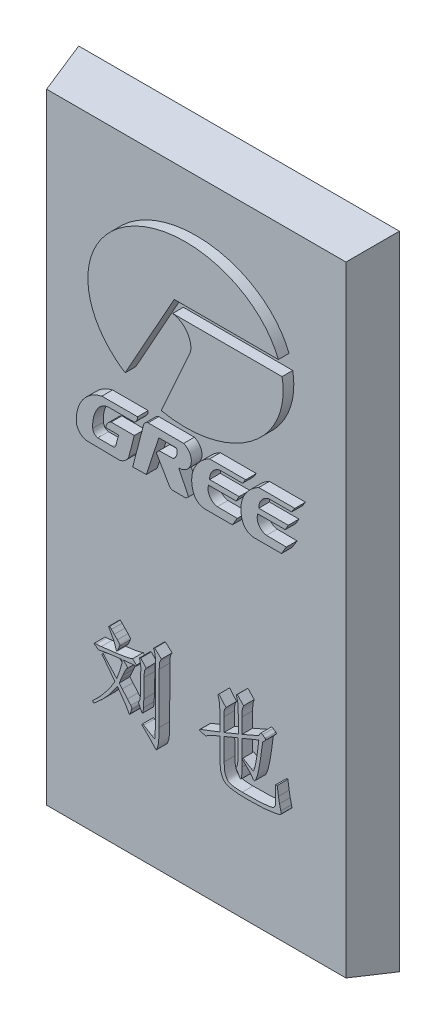
SolidWorks part; units mm, degrees
ref_plane "前视基准面" through (0, 0, 0) normal (0, 0, 1) x (1, 0, 0)
ref_plane "上视基准面" through (0, 0, 0) normal (0, 1, 0) x (1, 0, 0)
ref_plane "右视基准面" through (0, 0, 0) normal (1, 0, 0) x (0, 0, -1)
other "Configuration Table"
sketch "草图1" plane through (0, 0, 0) normal (0, 0, 1) x (1, 0, 0)
  line L18 (-15, -30) -> (15, -30)
  line L19 (-15, -30) -> (-15, 30)
  line L20 (-15, 30) -> (15, 30)
  line L21 (15, -30) -> (15, 30)
  line L22 (-15, -30) -> (15, 30) construction
  line L23 (-15, 30) -> (15, -30) construction
  point P0 (0, 0)
  dimension "D2" = 60
  dimension "D1" = 30
ref_plane "基准面1" through (0, 0, 4) normal (0, 0, 1) x (1, 0, 0)
sketch "草图2" plane through (0, 0, 4) normal (0, 0, 1) x (1, 0, 0)
  line L0 (-15, 30) -> (15, 30) construction
  line L1 (-14, -29) -> (14, -29)
  line L2 (-14, -29) -> (-14, 29)
  line L3 (-14, 29) -> (14, 29)
  line L4 (14, -29) -> (14, 29)
  line L5 (-14, -29) -> (14, 29) construction
  line L6 (-14, 29) -> (14, -29) construction
  line L7 (15, -30) -> (15, 30) construction
  point P0 (0, 0)
  dimension "D1" = 1
  dimension "D2" = 1
loft "放样1" add profiles "草图1", "草图2"
sketch "草图4" plane through (0, 0, 4) normal (0, 0, 1) x (1, 0, 0)
  line L6 (-14, -17) -> (14, -17) construction
  line L7 (-14, -29) -> (-14, 29) construction
  line L8 (14, -29) -> (14, 29) construction
  text T0 "刘也" font "汉仪长仿宋体" height 6
  dimension "D1" = 17
extrude "凸台-拉伸3" add sketch "草图4" along normal blind 1
sketch "草图5" plane through (0, 0, 0) normal (0, 0, -1) x (-1, 0, 0)
  line L4 (0, 18) -> (0, 0) construction
  line L5 (0, 0) -> (0, -18) construction
  line L6 (15, -30) -> (-15, -30) construction
  circle A7 centre (0, 0) radius 5.5
  circle A8 centre (0, 18) radius 5.5
  circle A9 centre (0, -18) radius 5.5
  dimension "D1" = 11
  dimension "D2" = 12
extrude "切除-拉伸1" cut sketch "草图5" against normal blind 2
sketch "草图7" plane through (0, 0, 4) normal (0, 0, 1) x (1, 0, 0)
  line L0 (3.2108, -13.9623) -> (1.3838, -14.6693) construction
  line L1 (1.3838, -14.8163) -> (1.8889, -14.9544) construction
  line L2 (3.2223, -14.2896) -> (3.2338, -16.284) construction
  line L3 (8.9065, -17.5088) -> (8.7864, -16.9911) construction
  line L4 (8.7864, -16.9911) -> (8.6892, -16.4387) construction
  line L5 (8.6892, -16.4387) -> (8.569, -15.6192) construction
  line L6 (8.569, -15.6192) -> (8.4258, -15.6358) construction
  line L7 (8.4258, -15.6358) -> (8.413, -17.2071) construction
  line L8 (3.6072, -16.1882) -> (3.5944, -14.1349) construction
  line L9 (3.5944, -14.1349) -> (4.9163, -13.5826) construction
  line L10 (4.9163, -13.5826) -> (4.9163, -14.7997) construction
  line L11 (4.832, -16.3186) -> (4.9892, -16.6024) construction
  line L12 (5.2654, -15.7918) -> (5.2654, -13.4445) construction
  line L13 (5.2654, -13.4445) -> (6.8507, -12.7976) construction
  line L14 (6.1782, -15.4901) -> (5.3728, -14.9979) construction
  line L15 (5.3728, -14.9979) -> (5.3012, -15.127) construction
  line L16 (5.3012, -15.127) -> (5.6131, -15.4211) construction
  line L17 (5.6131, -15.4211) -> (5.9737, -15.7918) construction
  line L18 (5.9737, -15.7918) -> (6.2984, -16.1971) construction
  line L19 (7.4401, -12.3744) -> (7.1882, -12.1839) construction
  line L20 (7.0195, -12.1583) -> (6.8277, -12.4524) construction
  line L21 (6.8277, -12.4524) -> (5.2769, -13.1249) construction
  line L22 (5.2769, -13.1249) -> (5.2769, -11.7185) construction
  line L23 (5.4214, -10.7341) -> (4.832, -10.1127) construction
  line L24 (4.832, -10.1127) -> (4.7361, -10.1997) construction
  line L25 (4.9291, -11.753) -> (4.9291, -13.2629) construction
  line L26 (4.9291, -13.2629) -> (3.5829, -13.8242) construction
  line L27 (3.5829, -13.8242) -> (3.5829, -12.547) construction
  line L28 (3.7746, -11.7006) -> (3.1149, -10.9412) construction
  line L29 (3.1149, -10.9412) -> (3.0178, -11.0447) construction
  line L30 (3.2108, -12.3744) -> (3.2108, -13.9623) construction
  line L31 (-2.8861, -10.2163) -> (-2.9948, -10.2853) construction
  line L32 (-2.8017, -11.5459) -> (-2.826, -16.4822) construction
  line L33 (-3.138, -17.4488) -> (-3.9076, -16.9744) construction
  line L34 (-3.9076, -16.9744) -> (-4.0035, -16.9054) construction
  line L35 (-4.0035, -16.9054) -> (-4.0994, -17.0089) construction
  line L36 (-4.0994, -17.0089) -> (-3.9677, -17.1547) construction
  line L37 (-3.9677, -17.1547) -> (-3.3553, -17.7505) construction
  line L38 (-3.3553, -17.7505) -> (-2.9219, -18.2248) construction
  line L39 (-2.4898, -16.4643) -> (-2.4655, -11.7185) construction
  line L40 (-2.2609, -10.7954) -> (-2.8861, -10.2163) construction
  line L41 (-4.1838, -12.4434) -> (-4.1953, -12.8142) construction
  line L42 (-4.1953, -12.8142) -> (-4.2323, -14.6437) construction
  line L43 (-4.3525, -15.5323) -> (-4.2554, -15.7138) construction
  line L44 (-4.2554, -15.7138) -> (-4.148, -15.9209) construction
  line L45 (-3.9434, -15.5847) -> (-3.9076, -14.8598) construction
  line L46 (-3.9076, -14.8598) -> (-3.8718, -13.0814) construction
  line L47 (-3.6915, -12.2453) -> (-4.1953, -11.675) construction
  line L48 (-4.1953, -11.675) -> (-4.3154, -11.7275) construction
  line L49 (-8.702, -17.3887) -> (-8.6061, -17.5344) construction
  line L50 (-8.6061, -17.5344) -> (-8.4731, -17.4309) construction
  line L51 (-5.5658, -16.215) -> (-5.4214, -16.4822) construction
  line L52 (-5.4214, -16.4822) -> (-5.3255, -16.6638) construction
  line L53 (-5.1695, -16.6638) -> (-5.0608, -16.2917) construction
  line L54 (-5.1209, -15.9734) -> (-5.4341, -15.6103) construction
  line L55 (-5.4341, -15.6103) -> (-5.9264, -15.049) construction
  line L56 (-5.9264, -15.049) -> (-6.214, -14.7128) construction
  line L57 (-6.214, -14.7128) -> (-6.0823, -14.411) construction
  line L58 (-6.0823, -14.411) -> (-5.8535, -13.8932) construction
  line L59 (-5.4098, -13.0993) -> (-5.7934, -12.6505) construction
  line L60 (-5.7934, -12.6505) -> (-5.1938, -12.5905) construction
  line L61 (-5.1938, -12.5905) -> (-4.6287, -12.547) construction
  line L62 (-4.5929, -12.4434) -> (-4.9649, -12.1238) construction
  line L63 (-7.885, -12.5905) -> (-8.3657, -12.625) construction
  line L64 (-8.4859, -12.7452) -> (-8.2328, -12.9356) construction
  line L65 (-8.2328, -12.9356) -> (-8.1612, -12.9957) construction
  line L66 (-8.1612, -12.9957) -> (-7.9566, -12.9523) construction
  line L67 (-7.9566, -12.9523) -> (-7.4516, -12.8577) construction
  line L68 (-7.4516, -12.8577) -> (-6.9722, -12.7886) construction
  line L69 (-6.9722, -12.7886) -> (-5.9506, -12.6672) construction
  line L70 (-5.9506, -12.6672) -> (-5.9506, -12.8577) construction
  line L71 (-7.6447, -13.1594) -> (-7.729, -13.0737) construction
  line L72 (-7.729, -13.0737) -> (-7.8249, -13.1773) construction
  line L73 (-7.8249, -13.1773) -> (-7.729, -13.3064) construction
  line L74 (-8.6176, -17.3017) -> (-8.702, -17.3887) construction
  line L75 (-7.2113, -10.6305) -> (-7.1154, -10.7775) construction
  line L76 (-6.9722, -11.0537) -> (-6.8034, -11.3554) construction
  line L77 (-6.5273, -12.0292) -> (-6.503, -12.1149) construction
  line L78 (-6.3112, -12.0292) -> (-6.191, -11.7185) construction
  line L79 (-6.3828, -11.2953) -> (-6.6717, -10.9936) construction
  line L80 (-6.6717, -10.9936) -> (-6.9351, -10.7264) construction
  line L81 (-6.9351, -10.7264) -> (-7.1039, -10.5538) construction
  line L82 (-7.1039, -10.5538) -> (-7.2113, -10.6305) construction
  line L83 (3.2108, -13.9623) -> (1.3838, -14.6693)
  line L84 (1.3838, -14.8163) -> (1.8889, -14.9544)
  line L85 (3.2223, -14.2896) -> (3.2338, -16.284)
  line L86 (8.9065, -17.5088) -> (8.7864, -16.9911)
  line L87 (8.7864, -16.9911) -> (8.6892, -16.4387)
  line L88 (8.6892, -16.4387) -> (8.569, -15.6192)
  line L89 (8.569, -15.6192) -> (8.4258, -15.6358)
  line L90 (8.4258, -15.6358) -> (8.413, -17.2071)
  line L91 (3.6072, -16.1882) -> (3.5944, -14.1349)
  line L92 (3.5944, -14.1349) -> (4.9163, -13.5826)
  line L93 (4.9163, -13.5826) -> (4.9163, -14.7997)
  line L94 (4.832, -16.3186) -> (4.9892, -16.6024)
  line L95 (5.2654, -15.7918) -> (5.2654, -13.4445)
  line L96 (5.2654, -13.4445) -> (6.8507, -12.7976)
  line L97 (6.1782, -15.4901) -> (5.3728, -14.9979)
  line L98 (5.3728, -14.9979) -> (5.3012, -15.127)
  line L99 (5.3012, -15.127) -> (5.6131, -15.4211)
  line L100 (5.6131, -15.4211) -> (5.9737, -15.7918)
  line L101 (5.9737, -15.7918) -> (6.2984, -16.1971)
  line L102 (7.4401, -12.3744) -> (7.1882, -12.1839)
  line L103 (7.0195, -12.1583) -> (6.8277, -12.4524)
  line L104 (6.8277, -12.4524) -> (5.2769, -13.1249)
  line L105 (5.2769, -13.1249) -> (5.2769, -11.7185)
  line L106 (5.4214, -10.7341) -> (4.832, -10.1127)
  line L107 (4.832, -10.1127) -> (4.7361, -10.1997)
  line L108 (4.9291, -11.753) -> (4.9291, -13.2629)
  line L109 (4.9291, -13.2629) -> (3.5829, -13.8242)
  line L110 (3.5829, -13.8242) -> (3.5829, -12.547)
  line L111 (3.7746, -11.7006) -> (3.1149, -10.9412)
  line L112 (3.1149, -10.9412) -> (3.0178, -11.0447)
  line L113 (3.2108, -12.3744) -> (3.2108, -13.9623)
  line L114 (-2.8861, -10.2163) -> (-2.9948, -10.2853)
  line L115 (-2.8017, -11.5459) -> (-2.826, -16.4822)
  line L116 (-3.138, -17.4488) -> (-3.9076, -16.9744)
  line L117 (-3.9076, -16.9744) -> (-4.0035, -16.9054)
  line L118 (-4.0035, -16.9054) -> (-4.0994, -17.0089)
  line L119 (-4.0994, -17.0089) -> (-3.9677, -17.1547)
  line L120 (-3.9677, -17.1547) -> (-3.3553, -17.7505)
  line L121 (-3.3553, -17.7505) -> (-2.9219, -18.2248)
  line L122 (-2.4898, -16.4643) -> (-2.4655, -11.7185)
  line L123 (-2.2609, -10.7954) -> (-2.8861, -10.2163)
  line L124 (-4.1838, -12.4434) -> (-4.1953, -12.8142)
  line L125 (-4.1953, -12.8142) -> (-4.2323, -14.6437)
  line L126 (-4.3525, -15.5323) -> (-4.2554, -15.7138)
  line L127 (-4.2554, -15.7138) -> (-4.148, -15.9209)
  line L128 (-3.9434, -15.5847) -> (-3.9076, -14.8598)
  line L129 (-3.9076, -14.8598) -> (-3.8718, -13.0814)
  line L130 (-3.6915, -12.2453) -> (-4.1953, -11.675)
  line L131 (-4.1953, -11.675) -> (-4.3154, -11.7275)
  line L132 (-8.702, -17.3887) -> (-8.6061, -17.5344)
  line L133 (-8.6061, -17.5344) -> (-8.4731, -17.4309)
  line L134 (-5.5658, -16.215) -> (-5.4214, -16.4822)
  line L135 (-5.4214, -16.4822) -> (-5.3255, -16.6638)
  line L136 (-5.1695, -16.6638) -> (-5.0608, -16.2917)
  line L137 (-5.1209, -15.9734) -> (-5.4341, -15.6103)
  line L138 (-5.4341, -15.6103) -> (-5.9264, -15.049)
  line L139 (-5.9264, -15.049) -> (-6.214, -14.7128)
  line L140 (-6.214, -14.7128) -> (-6.0823, -14.411)
  line L141 (-6.0823, -14.411) -> (-5.8535, -13.8932)
  line L142 (-5.4098, -13.0993) -> (-5.7934, -12.6505)
  line L143 (-5.7934, -12.6505) -> (-5.1938, -12.5905)
  line L144 (-5.1938, -12.5905) -> (-4.6287, -12.547)
  line L145 (-4.5929, -12.4434) -> (-4.9649, -12.1238)
  line L146 (-7.885, -12.5905) -> (-8.3657, -12.625)
  line L147 (-8.4859, -12.7452) -> (-8.2328, -12.9356)
  line L148 (-8.2328, -12.9356) -> (-8.1612, -12.9957)
  line L149 (-8.1612, -12.9957) -> (-7.9566, -12.9523)
  line L150 (-7.9566, -12.9523) -> (-7.4516, -12.8577)
  line L151 (-7.4516, -12.8577) -> (-6.9722, -12.7886)
  line L152 (-6.9722, -12.7886) -> (-5.9506, -12.6672)
  line L153 (-5.9506, -12.6672) -> (-5.9506, -12.8577)
  line L154 (-7.6447, -13.1594) -> (-7.729, -13.0737)
  line L155 (-7.729, -13.0737) -> (-7.8249, -13.1773)
  line L156 (-7.8249, -13.1773) -> (-7.729, -13.3064)
  line L157 (-8.6176, -17.3017) -> (-8.702, -17.3887)
  line L158 (-7.2113, -10.6305) -> (-7.1154, -10.7775)
  line L159 (-6.9722, -11.0537) -> (-6.8034, -11.3554)
  line L160 (-6.5273, -12.0292) -> (-6.503, -12.1149)
  line L161 (-6.3112, -12.0292) -> (-6.191, -11.7185)
  line L162 (-6.3828, -11.2953) -> (-6.6717, -10.9936)
  line L163 (-6.6717, -10.9936) -> (-6.9351, -10.7264)
  line L164 (-6.9351, -10.7264) -> (-7.1039, -10.5538)
  line L165 (-7.1039, -10.5538) -> (-7.2113, -10.6305)
  spline S0 degree 3 poles (-1033.717, 1696.6076) (14.5849, -31.3392) (2.3796, -13.84) (1.322, -14.7057) (1.3032, -14.7272) (1.2978, -14.7519) (1.3028, -14.776) (1.3219, -14.7941) (2.4833, -15.4174) (10.8456, 3.4261) (-689.6183, -1891.6231) knots -16.626684 -16.626684 -16.626684 -16.626684 0.172084 0.308952 0.423314 0.521848 0.615174 0.717267 0.839241 17.04599 17.04599 17.04599 17.04599 only from (1.3838, -14.6693) to (1.3838, -14.8163) construction
  spline S1 degree 3 poles (-1193.4267, 1588.4483) (4.6942, -35.4098) (-2.0793, -17.6856) (2.0886, -14.8069) (2.1786, -14.7467) (2.255, -14.7057) (2.3236, -14.6723) (2.394, -14.6406) (2.4842, -14.6016) (2.5935, -14.5536) (2.723, -14.4991) (2.8716, -14.4348) (21.1798, -6.8784) (36.675, 7.0863) (846.5091, -1827.4773) knots -9.913111 -9.913111 -9.913111 -9.913111 0.088354 0.168711 0.240996 0.305231 0.342298 0.393919 0.460114 0.539323 0.633116 0.74183 0.864014 40.342075 40.342075 40.342075 40.342075 only from (1.8889, -14.9544) to (3.2223, -14.2896) construction
  spline S2 degree 3 poles (-1996.6425, -26.0924) (21.1619, -1.4114) (2.9373, -9.1514) (3.2408, -16.6481) (3.2493, -16.8011) (3.2608, -16.9395) (3.287, -17.0743) (3.3282, -17.2177) (3.3889, -17.3745) (3.4475, -17.514) (3.5093, -17.6275) (3.5725, -17.7068) (3.6497, -17.778) (3.7401, -17.842) (3.8439, -17.8993) (3.961, -17.9489) (4.091, -17.9913) (4.2346, -18.0246) (4.3907, -18.0542) (4.5598, -18.0774) (4.7413, -18.0999) (4.9353, -18.1162) (5.1417, -18.1268) (5.3603, -18.1366) (17.0583, -18.3013) (28.6468, -3.9526) (45.2697, -2017.6338) knots -5.726077 -5.726077 -5.726077 -5.726077 0.051298 0.096629 0.136668 0.171139 0.205044 0.243843 0.287585 0.336355 0.362012 0.388335 0.415202 0.443856 0.474721 0.507699 0.543092 0.581467 0.622821 0.667242 0.714879 0.765695 0.819407 0.876414 0.936712 9.962298 9.962298 9.962298 9.962298 only from (3.2338, -16.284) to (5.8305, -18.1391) construction
  spline S3 degree 3 poles (-13.558, -2017.9262) (-16.1126, -3.2156) (-4.8916, -18.3162) (6.2967, -18.1363) (6.5077, -18.135) (6.702, -18.1289) (6.8797, -18.1244) (7.0413, -18.1179) (7.1862, -18.1106) (7.3593, -18.0983) (7.5693, -18.079) (7.8251, -18.0454) (8.0919, -18.0098) (8.3171, -17.9718) (8.4924, -17.939) (8.6085, -17.9125) (8.7077, -17.8849) (8.7894, -17.8553) (8.8564, -17.8272) (8.9046, -17.795) (9.7801, -17.0547) (-10.3073, -3.2872) (1708.116, -1071.7951) knots -10.275083 -10.275083 -10.275083 -10.275083 0.076298 0.147407 0.213324 0.274064 0.329613 0.379985 0.425587 0.465631 0.542665 0.62318 0.707468 0.794943 0.837249 0.874555 0.906545 0.933712 0.95606 0.97423 0.988354 1.993762 1.993762 1.993762 1.993762 only from (5.8305, -18.1391) to (8.9538, -17.7249) construction
  spline S4 degree 3 poles (1950.4824, 462.1548) (-3.6389, -24.2841) (9.4886, -19.2587) (8.928, -17.6283) (8.3828, -15.5017) (24.8318, -10.629) (-1966.0478, -332.6785) knots -22.527171 -22.527171 -22.527171 -22.527171 0.152758 0.441236 0.761695 29.779876 29.779876 29.779876 29.779876 only from (8.9538, -17.7249) to (8.9065, -17.5088) construction
  spline S5 degree 3 poles (1964.363, -433.7342) (-12.5579, -7.9686) (9.2006, -15.0961) (8.374, -17.3632) (8.3303, -17.4427) (8.2869, -17.5147) (8.228, -17.5691) (8.157, -17.6037) (8.0635, -17.637) (7.9458, -17.6647) (7.8043, -17.6919) (7.6382, -17.714) (7.4476, -17.7331) (7.1586, -17.7525) (6.7742, -17.7729) (6.2972, -17.7876) (-12.0936, -18.089) (-30.4237, 1.2715) (-38.3924, -2017.04) knots -2.060584 -2.060584 -2.060584 -2.060584 0.022746 0.046909 0.073942 0.103777 0.121266 0.144564 0.173661 0.209707 0.252274 0.302159 0.35908 0.423101 0.560508 0.702361 0.848718 16.964876 16.964876 16.964876 16.964876 only from (8.413, -17.2071) to (5.3012, -17.7939) construction
  spline S6 degree 3 poles (-46.7827, -2016.9641) (22.8077, 5.2469) (13.3561, -18.3583) (4.7621, -17.7744) (4.5344, -17.7516) (4.3394, -17.7124) (4.1743, -17.6679) (4.0418, -17.6087) (3.9373, -17.5417) (3.8494, -17.4317) (3.7799, -17.2879) (3.7089, -17.1204) (3.6584, -16.9548) (3.628, -16.7397) (3.0291, -6.34) (22.0683, 4.4844) (-1996.1462, -34.556) knots -8.866171 -8.866171 -8.866171 -8.866171 0.102703 0.194721 0.275299 0.345385 0.405658 0.456275 0.49919 0.535795 0.603996 0.668093 0.728927 0.787086 0.898182 11.780137 11.780137 11.780137 11.780137 only from (5.3012, -17.7939) to (3.6072, -16.1882) construction
  spline S7 degree 3 poles (2004.3322, 28.2132) (-5.4357, 8.8885) (4.9939, -3.0766) (4.9157, -15.1159) (4.913, -15.2229) (4.9105, -15.3009) (4.9062, -15.3675) (4.8976, -15.4411) (4.8881, -15.5311) (4.8742, -15.6326) (4.8595, -15.7344) (4.8403, -15.8267) (4.8184, -15.904) (4.7924, -15.9663) (4.7664, -16.0149) (4.7485, -16.0553) (4.7377, -16.0864) (4.7267, -16.1124) (4.7369, -16.1442) (4.7545, -16.1874) (8.4419, -22.4311) (7.4888, -21.5343) (1094.0182, -1693.6924) knots -22.721442 -22.721442 -22.721442 -22.721442 0.117235 0.209236 0.277643 0.321637 0.358354 0.405016 0.463185 0.53135 0.600551 0.659631 0.71141 0.753745 0.788334 0.81677 0.837638 0.852065 0.86867 0.898605 0.942334 14.623876 14.623876 14.623876 14.623876 only from (4.9163, -14.7997) to (4.832, -16.3186) construction
  spline S8 degree 3 poles (-1550.7197, -1273.4139) (19.3456, 2.9931) (3.2309, -14.1918) (5.0799, -16.7505) (5.7712, -17.6613) (19.4263, 1.9782) (-1061.0354, -1708.7198) knots -34.275912 -34.275912 -34.275912 -34.275912 0.381659 0.667499 0.869536 12.383747 12.383747 12.383747 12.383747 only from (4.9892, -16.6024) to (5.1567, -16.8095) construction
  spline S9 degree 3 poles (918.7555, -1795.635) (-5.5243, 1.4675) (4.8071, -17.3305) (5.1958, -16.7827) (5.2129, -16.7483) (5.2282, -16.7063) (5.2394, -16.6557) (5.2459, -16.5944) (5.2522, -16.5121) (5.257, -16.4089) (5.2608, -16.2845) (5.2627, -16.1391) (5.4392, -7.5851) (-9.7444, 1.0472) (2005.1553, -7.1429) knots -1.687714 -1.687714 -1.687714 -1.687714 0.017456 0.042472 0.079552 0.130072 0.168818 0.227795 0.306061 0.404936 0.523255 0.662264 0.820778 24.999128 24.999128 24.999128 24.999128 only from (5.1567, -16.8095) to (5.2654, -15.7918) construction
  spline S10 degree 3 poles (1999.4433, -182.4933) (-0.9536, 17.1275) (8.3501, 1.4035) (6.8086, -13.2123) (6.7917, -13.371) (6.7732, -13.5025) (6.7549, -13.6268) (6.7362, -13.7638) (6.7125, -13.9226) (6.6791, -14.1669) (6.6279, -14.4944) (6.5596, -14.8224) (6.5056, -15.0718) (6.4665, -15.2245) (6.4351, -15.3421) (6.405, -15.4266) (6.3778, -15.4844) (6.3562, -15.5253) (6.3378, -15.5519) (6.3166, -15.5656) (6.2921, -15.5599) (6.2639, -15.5443) (4.0424, -14.2877) (11.2127, 0.4883) (-1139.8748, -1654.3969) knots -14.529546 -14.529546 -14.529546 -14.529546 0.077669 0.143357 0.196643 0.237586 0.276416 0.322552 0.376056 0.437289 0.569617 0.708128 0.772877 0.82528 0.866104 0.894742 0.914992 0.930089 0.941025 0.94733 0.953792 0.964678 0.979985 3.500837 3.500837 3.500837 3.500837 only from (6.8507, -12.7976) to (6.1782, -15.4901) construction
  spline S11 degree 3 poles (-1459.7871, -1376.4789) (16.124, -1.0165) (4.8212, -14.6345) (6.361, -16.2729) (7.1105, -16.8641) (15.6434, 1.6427) (-747.2579, -1868.7131) knots -40.720986 -40.720986 -40.720986 -40.720986 0.346655 0.629517 0.83833 17.401909 17.401909 17.401909 17.401909 only from (6.2984, -16.1971) to (6.4186, -16.3007) construction
  spline S12 degree 3 poles (837.9651, -1835.1249) (-8.1419, 10.6055) (5.776, -17.2113) (6.5025, -16.2565) (6.528, -16.2095) (6.5563, -16.1512) (6.5901, -16.0734) (6.631, -15.9775) (6.6736, -15.8661) (6.7146, -15.7421) (6.7515, -15.6071) (6.7856, -15.4601) (6.8204, -15.2999) (6.8542, -15.124) (6.8917, -14.9328) (6.9306, -14.7215) (6.9732, -14.4828) (7.0122, -14.2083) (7.0571, -13.8958) (7.0902, -13.6158) (7.1179, -13.389) (7.1385, -13.2361) (7.1567, -13.1048) (7.1715, -12.9952) (7.1853, -12.9069) (7.1977, -12.8407) (7.2081, -12.7966) (7.217, -12.763) (7.2413, -12.7362) (7.2737, -12.7029) (7.3166, -12.6607) (7.3686, -12.617) (7.4169, -12.5708) (7.4586, -12.5329) (7.4821, -12.4989) (7.4993, -12.4634) (7.0362, -10.9223) (-17.6107, -31.0912) (1493.2118, 1326.3414) knots -0.749252 -0.749252 -0.749252 -0.749252 0.011116 0.024256 0.034759 0.050015 0.070334 0.09545 0.124469 0.15558 0.188759 0.224443 0.263394 0.305925 0.352459 0.40264 0.459525 0.525733 0.60077 0.685168 0.727217 0.76409 0.795449 0.821898 0.843179 0.859308 0.869947 0.875726 0.883767 0.895184 0.909185 0.926664 0.943691 0.957044 0.966676 0.973237 0.984469 2.007557 2.007557 2.007557 2.007557 only from (6.4186, -16.3007) to (7.4401, -12.3744) construction
  spline S13 degree 3 poles (902.0496, 1776.4099) (0.6886, -34.6242) (9.0767, -12.9356) (7.086, -12.1281) (6.1315, -12.1467) (19.65, -37.5566) (-984.4161, 1724.6464) knots -32.736634 -32.736634 -32.736634 -32.736634 0.367152 0.634154 0.821366 13.935133 13.935133 13.935133 13.935133 only from (7.1882, -12.1839) to (7.0195, -12.1583) construction
  spline S14 degree 3 poles (-1994.6009, 0.495) (23.7054, -26.4113) (4.9761, -18.7485) (5.2835, -11.3643) (5.2914, -11.232) (5.3038, -11.1262) (5.3257, -11.034) (5.3512, -10.9406) (6.9792, -5.8121) (22.7426, -5.6507) (-1877.5534, 663.1337) knots -21.608795 -21.608795 -21.608795 -21.608795 0.198899 0.364768 0.496393 0.59539 0.682927 0.77943 0.885076 16.774062 16.774062 16.774062 16.774062 only from (5.2769, -11.7185) to (5.4214, -10.7341) construction
  spline S15 degree 3 poles (1902.8334, 619.7227) (-16.1551, -6.6372) (3.4236, -5.5784) (4.816, -10.4468) (4.8463, -10.5591) (4.8758, -10.7012) (4.902, -10.8854) (4.9158, -11.0799) (4.9214, -11.254) (4.9279, -11.4048) (4.905, -22.6176) (16.3078, -33.5295) (-1993.4919, -88.7053) knots -9.399112 -9.399112 -9.399112 -9.399112 0.086759 0.167144 0.240968 0.308143 0.443474 0.594867 0.67934 0.775169 0.882309 22.030604 22.030604 22.030604 22.030604 only from (4.7361, -10.1997) to (4.9291, -11.753) construction
  spline S16 degree 3 poles (-1996.3066, -6.3279) (21.0986, -26.1786) (3.2376, -19.0978) (3.5925, -12.2086) (3.6071, -12.0674) (3.6279, -11.9648) (3.6579, -11.8939) (3.6875, -11.8361) (6.3076, -7.6291) (19.1276, -10.4641) (-1635.6374, 1133.6983) knots -22.753125 -22.753125 -22.753125 -22.753125 0.200316 0.389353 0.554689 0.680516 0.74126 0.814082 0.900083 17.48624 17.48624 17.48624 17.48624 only from (3.5829, -12.547) to (3.7746, -11.7006) construction
  spline S17 degree 3 poles (1903.9912, 610.2623) (-20.7158, -5.6325) (1.4769, -5.2348) (3.1267, -11.4022) (3.1599, -11.5753) (3.1876, -11.7958) (3.8456, -21.4883) (-18.235, -31.7664) (2002.9406, 15.7492) knots -13.754831 -13.754831 -13.754831 -13.754831 0.142454 0.27858 0.408689 0.533703 0.771853 21.965234 21.965234 21.965234 21.965234 only from (3.0178, -11.0447) to (3.2108, -12.3744) construction
  spline S18 degree 3 poles (1863.0803, 709.0915) (-22.3797, -4.1401) (-5.0305, -4.4694) (-2.8997, -10.5404) (-2.8683, -10.6465) (-2.844, -10.7698) (-2.829, -10.9212) (-2.8225, -11.0733) (-2.8168, -11.193) (-2.8154, -11.2703) (-2.8106, -11.3328) (-2.8079, -11.3968) (-2.5223, -14.669) (-19.2275, -18.627) (1995.8178, 61.3832) knots -14.7087 -14.7087 -14.7087 -14.7087 0.116167 0.216181 0.30306 0.374052 0.509134 0.657525 0.72919 0.788892 0.837713 0.875556 0.938334 8.497053 8.497053 8.497053 8.497053 only from (-2.9948, -10.2853) to (-2.8017, -11.5459) construction
  spline S19 degree 3 poles (1996.6884, -57.1725) (-15.54, -4.2723) (-2.5643, -10.6635) (-2.8326, -16.6987) (-2.8349, -16.7929) (-2.8368, -16.8769) (-2.8416, -16.9497) (-2.8431, -17.0124) (-2.8477, -17.0639) (-2.8518, -17.1377) (-2.8594, -17.2275) (-2.8586, -17.3285) (-2.6706, -19.1698) (-24.0229, -19.8512) (1993.9836, -127.1361) knots -18.086944 -18.086944 -18.086944 -18.086944 0.116901 0.223456 0.319585 0.404033 0.479451 0.541837 0.595221 0.636857 0.766948 0.869544 0.944906 6.362298 6.362298 6.362298 6.362298 only from (-2.826, -16.4822) to (-2.8618, -17.4654) construction
  spline S20 degree 3 poles (1920.7346, -564.8783) (-19.9028, -9.0246) (-2.2232, -15.9139) (-2.8844, -17.541) (-2.8944, -17.5636) (-2.9124, -17.5786) (-2.943, -17.5624) (-2.9871, -17.5419) (-7.9881, -14.4729) (-0.924, -15.4233) (-1899.5268, 617.8288) knots -13.418067 -13.418067 -13.418067 -13.418067 0.123946 0.216991 0.278308 0.31908 0.381479 0.515917 0.721003 45.525651 45.525651 45.525651 45.525651 only from (-2.8618, -17.4654) to (-3.138, -17.4488) construction
  spline S21 degree 3 poles (194.9213, -2008.3902) (-15.0275, 1.5883) (-8.4676, -12.6222) (-2.8057, -18.3428) (-2.0182, -19.0945) (7.0662, -6.6445) (-1066.911, -1711.4586) knots -97.933846 -97.933846 -97.933846 -97.933846 0.408799 0.710783 0.906834 13.513962 13.513962 13.513962 13.513962 only from (-2.9219, -18.2248) to (-2.7416, -18.3897) construction
  spline S22 degree 3 poles (1541.3019, -1289.3663) (-17.2182, -8.6749) (-3.0151, -19.2135) (-2.6957, -18.315) (-2.6594, -18.2339) (-2.6181, -18.1202) (-2.5776, -17.9866) (-2.5431, -17.8417) (-2.5239, -17.6904) (-2.5098, -17.4826) (-2.5022, -17.2234) (-2.497, -16.9689) (-2.4939, -16.7788) (-2.491, -16.6565) (-2.4063, -10.64) (-11.8864, -4.6267) (1997.4337, -6.5983) knots -1.306783 -1.306783 -1.306783 -1.306783 0.011073 0.038994 0.08476 0.148534 0.222584 0.297979 0.375406 0.454948 0.615659 0.771094 0.84328 0.905715 0.957736 10.02345 10.02345 10.02345 10.02345 only from (-2.7416, -18.3897) to (-2.4898, -16.4643) construction
  spline S23 degree 3 poles (-2002.0433, 23.4082) (17.2178, -26.8655) (-2.9385, -18.8244) (-2.4518, -11.3454) (-2.4395, -11.2317) (-2.4299, -11.1629) (-2.4183, -11.1079) (-2.4062, -11.0612) (-2.3851, -11.014) (-2.3537, -10.9557) (0.2121, -6.3458) (14.755, -8.7652) (-1720.7414, 1012.1287) knots -22.788299 -22.788299 -22.788299 -22.788299 0.226747 0.424712 0.510059 0.582424 0.640662 0.684729 0.732249 0.801029 0.890645 17.139984 17.139984 17.139984 17.139984 only from (-2.4655, -11.7185) to (-2.2609, -10.7954) construction
  spline S24 degree 3 poles (1924.5555, 516.4873) (-21.4595, -4.1063) (-5.6484, -6.1098) (-4.2553, -11.9618) (-4.2351, -12.066) (-4.2157, -12.1849) (-3.2666, -19.1695) (-14.338, -27.5253) (1984.5585, 198.7689) knots -24.265145 -24.265145 -24.265145 -24.265145 0.176124 0.336499 0.483023 0.612769 0.832275 29.485687 29.485687 29.485687 29.485687 only from (-4.3154, -11.7275) to (-4.1838, -12.4434) construction
  spline S25 degree 3 poles (1993.4071, -111.1275) (-26.4009, -2.323) (-3.6574, -9.2924) (-4.2529, -14.9872) (-4.2827, -15.1305) (-4.3269, -15.2317) (-4.3657, -15.2981) (-4.3838, -15.3404) (-4.396, -15.3739) (-4.4028, -15.4128) (-3.7015, -17.7808) (17.82, -6.713) (-1681.3534, -1105.1804) knots -18.0051 -18.0051 -18.0051 -18.0051 0.201752 0.379581 0.534025 0.67384 0.735013 0.783251 0.822556 0.850486 0.909807 8.568288 8.568288 8.568288 8.568288 only from (-4.2323, -14.6437) to (-4.3525, -15.5323) construction
  spline S26 degree 3 poles (-1512.9602, -1328.6343) (10.4966, 3.2816) (-5.5522, -14.0466) (-4.0797, -16.0348) (-4.0465, -16.064) (-4.0156, -16.055) (-4.0025, -16.0314) (-3.9917, -16.0026) (-3.9815, -15.9618) (-3.9734, -15.9091) (-3.9642, -15.8448) (-3.9571, -15.7684) (-3.4918, -10.72) (-16.7031, -4.6524) (1991.2791, -152.9923) knots -10.887367 -10.887367 -10.887367 -10.887367 0.121964 0.207693 0.260892 0.300142 0.329863 0.376288 0.436469 0.514652 0.611416 0.722891 0.853081 22.971798 22.971798 22.971798 22.971798 only from (-4.148, -15.9209) to (-3.9434, -15.5847) construction
  spline S27 degree 3 poles (1994.0865, -101.0049) (-13.6723, -29.9635) (-3.8891, -21.5767) (-3.8702, -12.858) (-3.866, -12.7715) (-3.86, -12.6843) (-3.8474, -12.597) (-3.8347, -12.516) (-3.8137, -12.4521) (-3.7836, -12.3943) (-1.8693, -9.0083) (15.3369, -14.8877) (-1709.4277, 1031.8458) knots -29.538415 -29.538415 -29.538415 -29.538415 0.141799 0.263135 0.361172 0.438866 0.562703 0.663904 0.719374 0.792594 0.886876 14.061788 14.061788 14.061788 14.061788 only from (-3.8718, -13.0814) to (-3.6915, -12.2453) construction
  spline S28 degree 3 poles (1264.9967, -1559.4891) (-31.5873, -12.0786) (-13.6284, -22.0641) (-8.1342, -17.1422) (-7.9369, -16.9598) (-7.7283, -16.7545) (-7.5206, -16.5461) (-7.3343, -16.3462) (-7.1732, -16.1672) (-7.0581, -16.0237) (-6.9736, -15.91) (-6.9052, -15.8183) (-6.8336, -15.7144) (-6.7531, -15.6022) (-6.67, -15.4779) (-6.5781, -15.3451) (2.1562, -2.044) (17.435, 6.7071) (-1628.834, 1154.0726) knots -6.726074 -6.726074 -6.726074 -6.726074 0.062764 0.136145 0.220514 0.315903 0.411855 0.497633 0.57328 0.638674 0.670791 0.706683 0.746446 0.789663 0.836764 0.887318 0.941766 15.825984 15.825984 15.825984 15.825984 only from (-8.4731, -17.4309) to (-6.3828, -15.049) construction
  spline S29 degree 3 poles (-1774.7239, -949.3367) (-0.7487, -7.6484) (-7.3553, -13.3952) (-6.347, -15.1129) (-6.313, -15.1624) (-6.2693, -15.2266) (-6.2164, -15.3059) (-6.1504, -15.3976) (-6.0752, -15.5038) (-5.9929, -15.6196) (-5.909, -15.7352) (-5.8309, -15.8422) (-5.7637, -15.9368) (-5.7051, -16.0177) (-5.6581, -16.0866) (-5.617, -16.1403) (-2.5499, -20.6038) (-3.1453, -27.2731) (1710.5712, 1010.7307) knots -4.10249 -4.10249 -4.10249 -4.10249 0.017268 0.047445 0.089524 0.143804 0.211032 0.29024 0.381658 0.485286 0.589437 0.682632 0.764344 0.833847 0.893123 0.939986 0.976096 12.299151 12.299151 12.299151 12.299151 only from (-6.3828, -15.049) to (-5.5658, -16.215) construction
  spline S30 degree 3 poles (-1652.1034, -1151.5707) (8.8374, -2.9824) (-6.3284, -15.4657) (-5.2823, -16.7295) (-5.2616, -16.749) (-5.239, -16.7551) (-5.2169, -16.7491) (-5.1987, -16.7299) (-4.4002, -15.3061) (-20.3074, -6.3517) (1819.6509, -834.9933) knots -19.315907 -19.315907 -19.315907 -19.315907 0.184014 0.329932 0.435758 0.52042 0.60011 0.698183 0.82936 20.217518 20.217518 20.217518 20.217518 only from (-5.3255, -16.6638) to (-5.1695, -16.6638) construction
  spline S31 degree 3 poles (1756.3388, -963.5015) (-15.7851, -19.7388) (-6.0338, -20.2901) (-5.0347, -16.1894) (-5.0317, -16.153) (-5.0297, -16.1236) (-5.0402, -16.096) (-5.057, -16.0623) (-7.8026, -12.1779) (-16.0197, -15.5805) (1187.0566, 1589.806) knots -35.897109 -35.897109 -35.897109 -35.897109 0.175028 0.3144 0.421741 0.491694 0.565052 0.672076 0.818098 41.504706 41.504706 41.504706 41.504706 only from (-5.0608, -16.2917) to (-5.1209, -15.9734) construction
  spline S32 degree 3 poles (-1844.512, 772.8216) (-1.9985, -31.3954) (-8.803, -20.3942) (-5.7663, -13.6971) (-5.7298, -13.6114) (-5.6969, -13.5363) (-5.6669, -13.4717) (-5.6414, -13.4167) (-5.62, -13.3716) (-5.5873, -13.3017) (-3.5534, -10.1993) (22.2359, -28.7518) (-1476.7841, 1341.5083) knots -23.688236 -23.688236 -23.688236 -23.688236 0.124711 0.237544 0.339212 0.428998 0.50564 0.571681 0.627122 0.668853 0.823736 12.607364 12.607364 12.607364 12.607364 only from (-5.8535, -13.8932) to (-5.4098, -13.0993) construction
  spline S33 degree 3 poles (1048.4675, -1712.7468) (-20.15, 9.6222) (-5.0308, -13.2656) (-4.5787, -12.5119) (-4.4352, -11.4786) (-31.1321, -16.4036) (1947.3773, 423.0108) knots -17.330031 -17.330031 -17.330031 -17.330031 0.228603 0.460739 0.719052 22.488112 22.488112 22.488112 22.488112 only from (-4.6287, -12.547) to (-4.5929, -12.4434) construction
  spline S34 degree 3 poles (617.1539, -1912.8033) (1.0615, 6.6518) (0.4277, -10.6214) (-5.2524, -12.2113) (-5.4248, -12.2495) (-5.6173, -12.2898) (-5.8305, -12.3277) (-6.0647, -12.3642) (-16.7545, -13.9589) (-29.7673, 2.3999) (227.2617, -1998.576) knots -10.40378 -10.40378 -10.40378 -10.40378 0.082838 0.177515 0.284544 0.402898 0.534005 0.677173 0.832565 20.129151 20.129151 20.129151 20.129151 only from (-4.9649, -12.1238) to (-6.5873, -12.4345) construction
  spline S35 degree 3 poles (298.0282, -1988.6784) (34.5431, 3.4816) (14.3568, -9.9504) (-7.256, -12.5157) (-26.2506, -14.8362) (-46.4544, -6.0355) (171.7781, -2004.1497) knots -49.192308 -49.192308 -49.192308 -49.192308 0.264132 0.518317 0.763645 44.186385 44.186385 44.186385 44.186385 only from (-6.5873, -12.4345) to (-7.885, -12.5905) construction
  spline S36 degree 3 poles (-1461.4057, 1361.6465) (11.9395, -25.8139) (-5.9466, -12.0262) (-8.5083, -12.6493) (-8.5576, -12.6619) (-8.5585, -12.6948) (-6.6522, -14.1057) (-12.4698, 0.822) (848.919, -1819.5851) knots -27.163084 -27.163084 -27.163084 -27.163084 0.274008 0.539418 0.638409 0.701183 0.813539 22.170768 22.170768 22.170768 22.170768 only from (-8.3657, -12.625) to (-8.4859, -12.7452) construction
  spline S37 degree 3 poles (1980.3886, -245.9002) (-25.6618, -4.0136) (-5.2924, -9.814) (-5.9842, -13.0963) (-6.0243, -13.2582) (-6.0787, -13.4503) (-6.1499, -13.6689) (-6.2318, -13.9123) (-11.99, -28.9406) (-30.0035, -38.8194) (1823.522, -820.849) knots -5.750981 -5.750981 -5.750981 -5.750981 0.058152 0.137295 0.236273 0.356767 0.494511 0.647688 0.816423 29.295179 29.295179 29.295179 29.295179 only from (-5.9506, -12.8577) to (-6.4429, -14.4545) construction
  spline S38 degree 3 poles (-1440.4806, -1408.4344) (12.2022, -13.7825) (-2.3288, -18.9321) (-6.635, -14.2521) (-6.7478, -14.1367) (-6.9051, -13.9638) (-7.1046, -13.7457) (-7.3024, -13.5363) (-7.4406, -13.3794) (-7.5273, -13.2883) (-11.1426, -9.2579) (-21.1289, -11.1301) (1455.1445, 1350.6897) knots -10.550678 -10.550678 -10.550678 -10.550678 0.072662 0.155077 0.246174 0.346541 0.551898 0.74801 0.835624 0.906789 0.961595 10.027963 10.027963 10.027963 10.027963 only from (-6.4429, -14.4545) to (-7.6447, -13.1594) construction
  spline S39 degree 3 poles (-1690.9874, -1093.1833) (3.3964, -3.003) (-8.5702, -12.3185) (-7.6792, -13.3782) (-7.6356, -13.4372) (-7.5827, -13.4978) (-7.5262, -13.5706) (-7.4574, -13.6543) (-7.3699, -13.7703) (-7.2605, -13.9156) (-7.1281, -14.0897) (-6.975, -14.2939) (4.9528, -30.4112) (25.9086, -39.6948) (-1573.915, -1256.6215) knots -2.148203 -2.148203 -2.148203 -2.148203 0.015763 0.043388 0.082758 0.134752 0.173579 0.232037 0.310356 0.408975 0.526794 0.664916 0.822376 33.019448 33.019448 33.019448 33.019448 only from (-7.729, -13.3064) to (-6.6116, -14.7818) construction
  spline S40 degree 3 poles (1720.3243, -1023.3234) (-16.1487, 18.5257) (-0.3829, -5.2401) (-7.063, -15.5177) (-7.2989, -15.8542) (-7.5036, -16.115) (-7.6664, -16.3087) (-7.7781, -16.444) (-7.8861, -16.5659) (-7.9856, -16.679) (-8.079, -16.7812) (-8.1654, -16.8734) (-8.2462, -16.9542) (-8.3206, -17.0243) (-8.3868, -17.0855) (-8.4452, -17.1383) (-8.4946, -17.184) (-8.5356, -17.2221) (-8.5675, -17.2534) (-8.5919, -17.2758) (-10.0031, -18.7121) (-13.9652, -17.5077) (1380.8721, -1455.6115) knots -10.967114 -10.967114 -10.967114 -10.967114 0.13677 0.268528 0.395276 0.51773 0.575816 0.629956 0.680367 0.726837 0.769636 0.808773 0.843982 0.87557 0.903536 0.927593 0.948568 0.965902 0.979597 0.98994 0.996647 2.846485 2.846485 2.846485 2.846485 only from (-6.6116, -14.7818) to (-8.6176, -17.3017) construction
  spline S41 degree 3 poles (-1863.6245, -754.3794) (4.4911, -3.082) (-7.7846, -9.5752) (-7.0741, -10.8691) (-4.3579, -16.0121) (12.1418, -14.6441) (-1809.0679, -878.3222) knots -13.550654 -13.550654 -13.550654 -13.550654 0.090846 0.287239 0.590215 56.191237 56.191237 56.191237 56.191237 only from (-7.1154, -10.7775) to (-6.9722, -11.0537) construction
  spline S42 degree 3 poles (1834.9168, 768.1255) (-43.4567, -10.4562) (24.5419, 1.0806) (-32.1871, -38.5399) (1852.1265, 726.1252) knots -30.614491 -30.614491 -30.614491 -30.614491 0.497436 31.719294 31.719294 31.719294 31.719294 only from (-6.8034, -11.3554) to (-6.5273, -12.0292) construction
  spline S43 degree 3 poles (-1865.1417, -750.4644) (10.0329, -1.5337) (-7.3015, -10.4965) (-6.4726, -12.1947) (-6.45, -12.2151) (-6.4207, -12.2124) (-6.395, -12.1889) (-6.3692, -12.1506) (-4.9295, -9.4946) (-20.1862, 0.6082) (1823.1195, -820.1308) knots -15.623058 -15.623058 -15.623058 -15.623058 0.147979 0.251119 0.323111 0.388004 0.477994 0.606878 0.779247 25.920813 25.920813 25.920813 25.920813 only from (-6.503, -12.1149) to (-6.3112, -12.0292) construction
  spline S44 degree 3 poles (-1912.8987, -615.0411) (10.2854, -11.3835) (-7.4086, -14.4578) (-6.1458, -11.6023) (-6.1514, -11.5735) (-6.1633, -11.5549) (-6.1798, -11.5283) (-6.2061, -11.4958) (-6.2388, -11.4549) (-6.28, -11.4078) (-12.3004, -4.7951) (-23.0878, -2.3486) (1486.2203, 1319.7709) knots -17.033327 -17.033327 -17.033327 -17.033327 0.164438 0.264555 0.289914 0.332187 0.391502 0.47307 0.575597 0.69724 0.838081 52.760377 52.760377 52.760377 52.760377 only from (-6.191, -11.7185) to (-6.3828, -11.2953) construction
  spline S45 degree 3 poles (1.3838, -14.6693) (1.3711, -14.6746) (1.3482, -14.6842) (1.322, -14.7057) (1.3032, -14.7272) (1.2978, -14.7519) (1.3028, -14.776) (1.3219, -14.7941) (1.3491, -14.8087) (1.3713, -14.8135) (1.3838, -14.8163) knots 0 0 0 0 0.172084 0.308952 0.423314 0.521848 0.615174 0.717267 0.839241 1 1 1 1
  spline S46 degree 3 poles (1.8889, -14.9544) (1.9235, -14.9272) (1.9897, -14.8752) (2.0886, -14.8069) (2.1786, -14.7467) (2.255, -14.7057) (2.3236, -14.6723) (2.394, -14.6406) (2.4842, -14.6016) (2.5935, -14.5536) (2.723, -14.4991) (2.8716, -14.4348) (3.0408, -14.365) (3.1597, -14.3156) (3.2223, -14.2896) knots 0 0 0 0 0.088354 0.168711 0.240996 0.305231 0.342298 0.393919 0.460114 0.539323 0.633116 0.74183 0.864014 1 1 1 1
  spline S47 degree 3 poles (3.2338, -16.284) (3.2338, -16.3497) (3.2337, -16.4733) (3.2408, -16.6481) (3.2493, -16.8011) (3.2608, -16.9395) (3.287, -17.0743) (3.3282, -17.2177) (3.3889, -17.3745) (3.4475, -17.514) (3.5093, -17.6275) (3.5725, -17.7068) (3.6497, -17.778) (3.7401, -17.842) (3.8439, -17.8993) (3.961, -17.9489) (4.091, -17.9913) (4.2346, -18.0246) (4.3907, -18.0542) (4.5598, -18.0774) (4.7413, -18.0999) (4.9353, -18.1162) (5.1417, -18.1268) (5.3603, -18.1366) (5.5914, -18.1398) (5.7495, -18.1394) (5.8305, -18.1391) knots 0 0 0 0 0.051298 0.096629 0.136668 0.171139 0.205044 0.243843 0.287585 0.336355 0.362012 0.388335 0.415202 0.443856 0.474721 0.507699 0.543092 0.581467 0.622821 0.667242 0.714879 0.765695 0.819407 0.876414 0.936712 1 1 1 1
  spline S48 degree 3 poles (5.8305, -18.1391) (5.9119, -18.1394) (6.0691, -18.1399) (6.2967, -18.1363) (6.5077, -18.135) (6.702, -18.1289) (6.8797, -18.1244) (7.0413, -18.1179) (7.1862, -18.1106) (7.3593, -18.0983) (7.5693, -18.079) (7.8251, -18.0454) (8.0919, -18.0098) (8.3171, -17.9718) (8.4924, -17.939) (8.6085, -17.9125) (8.7077, -17.8849) (8.7894, -17.8553) (8.8564, -17.8272) (8.9046, -17.795) (8.9417, -17.7637) (8.9501, -17.737) (8.9538, -17.7249) knots 0 0 0 0 0.076298 0.147407 0.213324 0.274064 0.329613 0.379985 0.425587 0.465631 0.542665 0.62318 0.707468 0.794943 0.837249 0.874555 0.906545 0.933712 0.95606 0.97423 0.988354 1 1 1 1
  spline S49 degree 3 poles (8.9538, -17.7249) (8.9519, -17.7138) (8.9463, -17.6816) (8.928, -17.6283) (8.9124, -17.5675) (8.9083, -17.5264) (8.9065, -17.5088) knots 0 0 0 0 0.152758 0.441236 0.761695 1 1 1 1
  spline S50 degree 3 poles (8.413, -17.2071) (8.4097, -17.2325) (8.4027, -17.2847) (8.374, -17.3632) (8.3303, -17.4427) (8.2869, -17.5147) (8.228, -17.5691) (8.157, -17.6037) (8.0635, -17.637) (7.9458, -17.6647) (7.8043, -17.6919) (7.6382, -17.714) (7.4476, -17.7331) (7.1586, -17.7525) (6.7742, -17.7729) (6.2972, -17.7876) (5.8045, -17.7956) (5.4708, -17.7945) (5.3012, -17.7939) knots 0 0 0 0 0.022746 0.046909 0.073942 0.103777 0.121266 0.144564 0.173661 0.209707 0.252274 0.302159 0.35908 0.423101 0.560508 0.702361 0.848718 1 1 1 1
  spline S51 degree 3 poles (5.3012, -17.7939) (5.2044, -17.7933) (5.0209, -17.792) (4.7621, -17.7744) (4.5344, -17.7516) (4.3394, -17.7124) (4.1743, -17.6679) (4.0418, -17.6087) (3.9373, -17.5417) (3.8494, -17.4317) (3.7799, -17.2879) (3.7089, -17.1204) (3.6584, -16.9548) (3.628, -16.7397) (3.6133, -16.4846) (3.6092, -16.2841) (3.6072, -16.1882) knots 0 0 0 0 0.102703 0.194721 0.275299 0.345385 0.405658 0.456275 0.49919 0.535795 0.603996 0.668093 0.728927 0.787086 0.898182 1 1 1 1
  spline S52 degree 3 poles (4.9163, -14.7997) (4.9164, -14.8611) (4.9166, -14.9706) (4.9157, -15.1159) (4.913, -15.2229) (4.9105, -15.3009) (4.9062, -15.3675) (4.8976, -15.4411) (4.8881, -15.5311) (4.8742, -15.6326) (4.8595, -15.7344) (4.8403, -15.8267) (4.8184, -15.904) (4.7924, -15.9663) (4.7664, -16.0149) (4.7485, -16.0553) (4.7377, -16.0864) (4.7267, -16.1124) (4.7369, -16.1442) (4.7545, -16.1874) (4.7897, -16.247) (4.8166, -16.2926) (4.832, -16.3186) knots 0 0 0 0 0.117235 0.209236 0.277643 0.321637 0.358354 0.405016 0.463185 0.53135 0.600551 0.659631 0.71141 0.753745 0.788334 0.81677 0.837638 0.852065 0.86867 0.898605 0.942334 1 1 1 1
  spline S53 degree 3 poles (4.9892, -16.6024) (5.0056, -16.6332) (5.0341, -16.6872) (5.0799, -16.7505) (5.1155, -16.7974) (5.1451, -16.8061) (5.1567, -16.8095) knots 0 0 0 0 0.381659 0.667499 0.869536 1 1 1 1
  spline S54 degree 3 poles (5.1567, -16.8095) (5.163, -16.8089) (5.1783, -16.8074) (5.1958, -16.7827) (5.2129, -16.7483) (5.2282, -16.7063) (5.2394, -16.6557) (5.2459, -16.5944) (5.2522, -16.5121) (5.257, -16.4089) (5.2608, -16.2845) (5.2627, -16.1391) (5.2662, -15.9725) (5.2657, -15.8545) (5.2654, -15.7918) knots 0 0 0 0 0.017456 0.042472 0.079552 0.130072 0.168818 0.227795 0.306061 0.404936 0.523255 0.662264 0.820778 1 1 1 1
  spline S55 degree 3 poles (6.8507, -12.7976) (6.8431, -12.8747) (6.8292, -13.0171) (6.8086, -13.2123) (6.7917, -13.371) (6.7732, -13.5025) (6.7549, -13.6268) (6.7362, -13.7638) (6.7125, -13.9226) (6.6791, -14.1669) (6.6279, -14.4944) (6.5596, -14.8224) (6.5056, -15.0718) (6.4665, -15.2245) (6.4351, -15.3421) (6.405, -15.4266) (6.3778, -15.4844) (6.3562, -15.5253) (6.3378, -15.5519) (6.3166, -15.5656) (6.2921, -15.5599) (6.2639, -15.5443) (6.2236, -15.5215) (6.1946, -15.5015) (6.1782, -15.4901) knots 0 0 0 0 0.077669 0.143357 0.196643 0.237586 0.276416 0.322552 0.376056 0.437289 0.569617 0.708128 0.772877 0.82528 0.866104 0.894742 0.914992 0.930089 0.941025 0.94733 0.953792 0.964678 0.979985 1 1 1 1
  spline S56 degree 3 poles (6.2984, -16.1971) (6.3096, -16.2123) (6.33, -16.2399) (6.361, -16.2729) (6.3897, -16.2956) (6.4098, -16.2991) (6.4186, -16.3007) knots 0 0 0 0 0.346655 0.629517 0.83833 1 1 1 1
  spline S57 degree 3 poles (6.4186, -16.3007) (6.4348, -16.3001) (6.4703, -16.2988) (6.5025, -16.2565) (6.528, -16.2095) (6.5563, -16.1512) (6.5901, -16.0734) (6.631, -15.9775) (6.6736, -15.8661) (6.7146, -15.7421) (6.7515, -15.6071) (6.7856, -15.4601) (6.8204, -15.2999) (6.8542, -15.124) (6.8917, -14.9328) (6.9306, -14.7215) (6.9732, -14.4828) (7.0122, -14.2083) (7.0571, -13.8958) (7.0902, -13.6158) (7.1179, -13.389) (7.1385, -13.2361) (7.1567, -13.1048) (7.1715, -12.9952) (7.1853, -12.9069) (7.1977, -12.8407) (7.2081, -12.7966) (7.217, -12.763) (7.2413, -12.7362) (7.2737, -12.7029) (7.3166, -12.6607) (7.3686, -12.617) (7.4169, -12.5708) (7.4586, -12.5329) (7.4821, -12.4989) (7.4993, -12.4634) (7.4845, -12.414) (7.4564, -12.389) (7.4401, -12.3744) knots 0 0 0 0 0.011116 0.024256 0.034759 0.050015 0.070334 0.09545 0.124469 0.15558 0.188759 0.224443 0.263394 0.305925 0.352459 0.40264 0.459525 0.525733 0.60077 0.685168 0.727217 0.76409 0.795449 0.821898 0.843179 0.859308 0.869947 0.875726 0.883767 0.895184 0.909185 0.926664 0.943691 0.957044 0.966676 0.973237 0.984469 1 1 1 1
  spline S58 degree 3 poles (7.1882, -12.1839) (7.1686, -12.1707) (7.1348, -12.1479) (7.086, -12.1281) (7.0415, -12.129) (7.0267, -12.1487) (7.0195, -12.1583) knots 0 0 0 0 0.367152 0.634154 0.821366 1 1 1 1
  spline S59 degree 3 poles (5.2769, -11.7185) (5.2768, -11.652) (5.2766, -11.5301) (5.2835, -11.3643) (5.2914, -11.232) (5.3038, -11.1262) (5.3257, -11.034) (5.3512, -10.9406) (5.3833, -10.8396) (5.4083, -10.7702) (5.4214, -10.7341) knots 0 0 0 0 0.198899 0.364768 0.496393 0.59539 0.682927 0.77943 0.885076 1 1 1 1
  spline S60 degree 3 poles (4.7361, -10.1997) (4.7515, -10.2425) (4.7812, -10.3252) (4.816, -10.4468) (4.8463, -10.5591) (4.8758, -10.7012) (4.902, -10.8854) (4.9158, -11.0799) (4.9214, -11.254) (4.9279, -11.4048) (4.9275, -11.5732) (4.9286, -11.6912) (4.9291, -11.753) knots 0 0 0 0 0.086759 0.167144 0.240968 0.308143 0.443474 0.594867 0.67934 0.775169 0.882309 1 1 1 1
  spline S61 degree 3 poles (3.5829, -12.547) (3.5833, -12.4877) (3.584, -12.3726) (3.5925, -12.2086) (3.6071, -12.0674) (3.6279, -11.9648) (3.6579, -11.8939) (3.6875, -11.8361) (3.728, -11.7711) (3.7583, -11.7253) (3.7746, -11.7006) knots 0 0 0 0 0.200316 0.389353 0.554689 0.680516 0.74126 0.814082 0.900083 1 1 1 1
  spline S62 degree 3 poles (3.0178, -11.0447) (3.0385, -11.1055) (3.0791, -11.2242) (3.1267, -11.4022) (3.1599, -11.5753) (3.1876, -11.7958) (3.2057, -12.0617) (3.2091, -12.2717) (3.2108, -12.3744) knots 0 0 0 0 0.142454 0.27858 0.408689 0.533703 0.771853 1 1 1 1
  spline S63 degree 3 poles (-2.9948, -10.2853) (-2.9766, -10.3317) (-2.9427, -10.4179) (-2.8997, -10.5404) (-2.8683, -10.6465) (-2.844, -10.7698) (-2.829, -10.9212) (-2.8225, -11.0733) (-2.8168, -11.193) (-2.8154, -11.2703) (-2.8106, -11.3328) (-2.8079, -11.3968) (-2.8019, -11.4661) (-2.8018, -11.5195) (-2.8017, -11.5459) knots 0 0 0 0 0.116167 0.216181 0.30306 0.374052 0.509134 0.657525 0.72919 0.788892 0.837713 0.875556 0.938334 1 1 1 1
  spline S64 degree 3 poles (-2.826, -16.4822) (-2.8267, -16.5206) (-2.828, -16.5939) (-2.8326, -16.6987) (-2.8349, -16.7929) (-2.8368, -16.8769) (-2.8416, -16.9497) (-2.8431, -17.0124) (-2.8477, -17.0639) (-2.8518, -17.1377) (-2.8594, -17.2275) (-2.8586, -17.3285) (-2.8508, -17.4052) (-2.8585, -17.4475) (-2.8618, -17.4654) knots 0 0 0 0 0.116901 0.223456 0.319585 0.404033 0.479451 0.541837 0.595221 0.636857 0.766948 0.869544 0.944906 1 1 1 1
  spline S65 degree 3 poles (-2.8618, -17.4654) (-2.8651, -17.4809) (-2.871, -17.508) (-2.8844, -17.541) (-2.8944, -17.5636) (-2.9124, -17.5786) (-2.943, -17.5624) (-2.9871, -17.5419) (-3.0556, -17.4999) (-3.1078, -17.4675) (-3.138, -17.4488) knots 0 0 0 0 0.123946 0.216991 0.278308 0.31908 0.381479 0.515917 0.721003 1 1 1 1
  spline S66 degree 3 poles (-2.9219, -18.2248) (-2.8984, -18.2487) (-2.8577, -18.2903) (-2.8057, -18.3428) (-2.7702, -18.3767) (-2.7486, -18.3866) (-2.7416, -18.3897) knots 0 0 0 0 0.408799 0.710783 0.906834 1 1 1 1
  spline S67 degree 3 poles (-2.7416, -18.3897) (-2.7358, -18.3853) (-2.7151, -18.3697) (-2.6957, -18.315) (-2.6594, -18.2339) (-2.6181, -18.1202) (-2.5776, -17.9866) (-2.5431, -17.8417) (-2.5239, -17.6904) (-2.5098, -17.4826) (-2.5022, -17.2234) (-2.497, -16.9689) (-2.4939, -16.7788) (-2.491, -16.6565) (-2.4895, -16.5538) (-2.4897, -16.492) (-2.4898, -16.4643) knots 0 0 0 0 0.011073 0.038994 0.08476 0.148534 0.222584 0.297979 0.375406 0.454948 0.615659 0.771094 0.84328 0.905715 0.957736 1 1 1 1
  spline S68 degree 3 poles (-2.4655, -11.7185) (-2.4644, -11.6456) (-2.4624, -11.5091) (-2.4518, -11.3454) (-2.4395, -11.2317) (-2.4299, -11.1629) (-2.4183, -11.1079) (-2.4062, -11.0612) (-2.3851, -11.014) (-2.3537, -10.9557) (-2.3119, -10.8805) (-2.279, -10.8256) (-2.2609, -10.7954) knots 0 0 0 0 0.226747 0.424712 0.510059 0.582424 0.640662 0.684729 0.732249 0.801029 0.890645 1 1 1 1
  spline S69 degree 3 poles (-4.3154, -11.7275) (-4.3041, -11.7687) (-4.2825, -11.8476) (-4.2553, -11.9618) (-4.2351, -12.066) (-4.2157, -12.1849) (-4.1988, -12.3094) (-4.1883, -12.4029) (-4.1838, -12.4434) knots 0 0 0 0 0.176124 0.336499 0.483023 0.612769 0.832275 1 1 1 1
  spline S70 degree 3 poles (-4.2323, -14.6437) (-4.2335, -14.706) (-4.2358, -14.8232) (-4.2529, -14.9872) (-4.2827, -15.1305) (-4.3269, -15.2317) (-4.3657, -15.2981) (-4.3838, -15.3404) (-4.396, -15.3739) (-4.4028, -15.4128) (-4.3868, -15.4671) (-4.3654, -15.5077) (-4.3525, -15.5323) knots 0 0 0 0 0.201752 0.379581 0.534025 0.67384 0.735013 0.783251 0.822556 0.850486 0.909807 1 1 1 1
  spline S71 degree 3 poles (-4.148, -15.9209) (-4.1355, -15.9459) (-4.1142, -15.9883) (-4.0797, -16.0348) (-4.0465, -16.064) (-4.0156, -16.055) (-4.0025, -16.0314) (-3.9917, -16.0026) (-3.9815, -15.9618) (-3.9734, -15.9091) (-3.9642, -15.8448) (-3.9571, -15.7684) (-3.949, -15.6807) (-3.9453, -15.618) (-3.9434, -15.5847) knots 0 0 0 0 0.121964 0.207693 0.260892 0.300142 0.329863 0.376288 0.436469 0.514652 0.611416 0.722891 0.853081 1 1 1 1
  spline S72 degree 3 poles (-3.8718, -13.0814) (-3.8713, -13.0401) (-3.8704, -12.9634) (-3.8702, -12.858) (-3.866, -12.7715) (-3.86, -12.6843) (-3.8474, -12.597) (-3.8347, -12.516) (-3.8137, -12.4521) (-3.7836, -12.3943) (-3.7433, -12.3231) (-3.7098, -12.2727) (-3.6915, -12.2453) knots 0 0 0 0 0.141799 0.263135 0.361172 0.438866 0.562703 0.663904 0.719374 0.792594 0.886876 1 1 1 1
  spline S73 degree 3 poles (-8.4731, -17.4309) (-8.4212, -17.3891) (-8.3086, -17.2985) (-8.1342, -17.1422) (-7.9369, -16.9598) (-7.7283, -16.7545) (-7.5206, -16.5461) (-7.3343, -16.3462) (-7.1732, -16.1672) (-7.0581, -16.0237) (-6.9736, -15.91) (-6.9052, -15.8183) (-6.8336, -15.7144) (-6.7531, -15.6022) (-6.67, -15.4779) (-6.5781, -15.3451) (-6.4829, -15.2003) (-6.4169, -15.1006) (-6.3828, -15.049) knots 0 0 0 0 0.062764 0.136145 0.220514 0.315903 0.411855 0.497633 0.57328 0.638674 0.670791 0.706683 0.746446 0.789663 0.836764 0.887318 0.941766 1 1 1 1
  spline S74 degree 3 poles (-6.3828, -15.049) (-6.379, -15.0563) (-6.3686, -15.0762) (-6.347, -15.1129) (-6.313, -15.1624) (-6.2693, -15.2266) (-6.2164, -15.3059) (-6.1504, -15.3976) (-6.0752, -15.5038) (-5.9929, -15.6196) (-5.909, -15.7352) (-5.8309, -15.8422) (-5.7637, -15.9368) (-5.7051, -16.0177) (-5.6581, -16.0866) (-5.617, -16.1403) (-5.5882, -16.1821) (-5.5722, -16.2056) (-5.5658, -16.215) knots 0 0 0 0 0.017268 0.047445 0.089524 0.143804 0.211032 0.29024 0.381658 0.485286 0.589437 0.682632 0.764344 0.833847 0.893123 0.939986 0.976096 1 1 1 1
  spline S75 degree 3 poles (-5.3255, -16.6638) (-5.3183, -16.6773) (-5.3054, -16.7016) (-5.2823, -16.7295) (-5.2616, -16.749) (-5.239, -16.7551) (-5.2169, -16.7491) (-5.1987, -16.7299) (-5.1825, -16.7009) (-5.1742, -16.6772) (-5.1695, -16.6638) knots 0 0 0 0 0.184014 0.329932 0.435758 0.52042 0.60011 0.698183 0.82936 1 1 1 1
  spline S76 degree 3 poles (-5.0608, -16.2917) (-5.0556, -16.2721) (-5.0463, -16.237) (-5.0347, -16.1894) (-5.0317, -16.153) (-5.0297, -16.1236) (-5.0402, -16.096) (-5.057, -16.0623) (-5.0862, -16.021) (-5.1085, -15.9904) (-5.1209, -15.9734) knots 0 0 0 0 0.175028 0.3144 0.421741 0.491694 0.565052 0.672076 0.818098 1 1 1 1
  spline S77 degree 3 poles (-5.8535, -13.8932) (-5.8382, -13.8583) (-5.8092, -13.7916) (-5.7663, -13.6971) (-5.7298, -13.6114) (-5.6969, -13.5363) (-5.6669, -13.4717) (-5.6414, -13.4167) (-5.62, -13.3716) (-5.5873, -13.3017) (-5.524, -13.2052) (-5.4495, -13.1361) (-5.4098, -13.0993) knots 0 0 0 0 0.124711 0.237544 0.339212 0.428998 0.50564 0.571681 0.627122 0.668853 0.823736 1 1 1 1
  spline S78 degree 3 poles (-4.6287, -12.547) (-4.6181, -12.5453) (-4.5967, -12.5419) (-4.5787, -12.5119) (-4.5737, -12.4761) (-4.5863, -12.4546) (-4.5929, -12.4434) knots 0 0 0 0 0.228603 0.460739 0.719052 1 1 1 1
  spline S79 degree 3 poles (-4.9649, -12.1238) (-5.0083, -12.1382) (-5.1012, -12.169) (-5.2524, -12.2113) (-5.4248, -12.2495) (-5.6173, -12.2898) (-5.8305, -12.3277) (-6.0647, -12.3642) (-6.3189, -12.4021) (-6.4957, -12.4234) (-6.5873, -12.4345) knots 0 0 0 0 0.082838 0.177515 0.284544 0.402898 0.534005 0.677173 0.832565 1 1 1 1
  spline S80 degree 3 poles (-6.5873, -12.4345) (-6.7015, -12.4486) (-6.9256, -12.4764) (-7.256, -12.5157) (-7.5743, -12.5545) (-7.7827, -12.5786) (-7.885, -12.5905) knots 0 0 0 0 0.264132 0.518317 0.763645 1 1 1 1
  spline S81 degree 3 poles (-8.3657, -12.625) (-8.3939, -12.6283) (-8.4495, -12.635) (-8.5083, -12.6493) (-8.5576, -12.6619) (-8.5585, -12.6948) (-8.5264, -12.7185) (-8.5015, -12.7349) (-8.4859, -12.7452) knots 0 0 0 0 0.274008 0.539418 0.638409 0.701183 0.813539 1 1 1 1
  spline S82 degree 3 poles (-5.9506, -12.8577) (-5.9525, -12.8901) (-5.9569, -12.9668) (-5.9842, -13.0963) (-6.0243, -13.2582) (-6.0787, -13.4503) (-6.1499, -13.6689) (-6.2318, -13.9123) (-6.3329, -14.176) (-6.4052, -14.3591) (-6.4429, -14.4545) knots 0 0 0 0 0.058152 0.137295 0.236273 0.356767 0.494511 0.647688 0.816423 1 1 1 1
  spline S83 degree 3 poles (-6.4429, -14.4545) (-6.4729, -14.424) (-6.5369, -14.3588) (-6.635, -14.2521) (-6.7478, -14.1367) (-6.9051, -13.9638) (-7.1046, -13.7457) (-7.3024, -13.5363) (-7.4406, -13.3794) (-7.5273, -13.2883) (-7.592, -13.2162) (-7.6293, -13.176) (-7.6447, -13.1594) knots 0 0 0 0 0.072662 0.155077 0.246174 0.346541 0.551898 0.74801 0.835624 0.906789 0.961595 1 1 1 1
  spline S84 degree 3 poles (-7.729, -13.3064) (-7.7246, -13.3151) (-7.7123, -13.3389) (-7.6792, -13.3782) (-7.6356, -13.4372) (-7.5827, -13.4978) (-7.5262, -13.5706) (-7.4574, -13.6543) (-7.3699, -13.7703) (-7.2605, -13.9156) (-7.1281, -14.0897) (-6.975, -14.2939) (-6.8013, -14.5286) (-6.6774, -14.6941) (-6.6116, -14.7818) knots 0 0 0 0 0.015763 0.043388 0.082758 0.134752 0.173579 0.232037 0.310356 0.408975 0.526794 0.664916 0.822376 1 1 1 1
  spline S85 degree 3 poles (-6.6116, -14.7818) (-6.6855, -14.9095) (-6.8306, -15.1601) (-7.063, -15.5177) (-7.2989, -15.8542) (-7.5036, -16.115) (-7.6664, -16.3087) (-7.7781, -16.444) (-7.8861, -16.5659) (-7.9856, -16.679) (-8.079, -16.7812) (-8.1654, -16.8734) (-8.2462, -16.9542) (-8.3206, -17.0243) (-8.3868, -17.0855) (-8.4452, -17.1383) (-8.4946, -17.184) (-8.5356, -17.2221) (-8.5675, -17.2534) (-8.5919, -17.2758) (-8.6074, -17.2915) (-8.615, -17.2992) (-8.6176, -17.3017) knots 0 0 0 0 0.13677 0.268528 0.395276 0.51773 0.575816 0.629956 0.680367 0.726837 0.769636 0.808773 0.843982 0.87557 0.903536 0.927593 0.948568 0.965902 0.979597 0.98994 0.996647 1 1 1 1
  spline S86 degree 3 poles (-7.1154, -10.7775) (-7.1126, -10.7866) (-7.1037, -10.8151) (-7.0741, -10.8691) (-7.0301, -10.9525) (-6.9933, -11.0167) (-6.9722, -11.0537) knots 0 0 0 0 0.090846 0.287239 0.590215 1 1 1 1
  spline S87 degree 3 poles (-6.8034, -11.3554) (-6.7496, -11.4639) (-6.6415, -11.6819) (-6.5655, -11.913) (-6.5273, -12.0292) knots 0 0 0 0 0.497436 1 1 1 1
  spline S88 degree 3 poles (-6.503, -12.1149) (-6.4979, -12.1317) (-6.4894, -12.1602) (-6.4726, -12.1947) (-6.45, -12.2151) (-6.4207, -12.2124) (-6.395, -12.1889) (-6.3692, -12.1506) (-6.3396, -12.0961) (-6.3214, -12.0532) (-6.3112, -12.0292) knots 0 0 0 0 0.147979 0.251119 0.323111 0.388004 0.477994 0.606878 0.779247 1 1 1 1
  spline S89 degree 3 poles (-6.191, -11.7185) (-6.1818, -11.6923) (-6.1669, -11.6501) (-6.1458, -11.6023) (-6.1514, -11.5735) (-6.1633, -11.5549) (-6.1798, -11.5283) (-6.2061, -11.4958) (-6.2388, -11.4549) (-6.28, -11.4078) (-6.3289, -11.354) (-6.364, -11.3158) (-6.3828, -11.2953) knots 0 0 0 0 0.164438 0.264555 0.289914 0.332187 0.391502 0.47307 0.575597 0.69724 0.838081 1 1 1 1
extrude "凸台-拉伸4" add sketch "草图7" along normal blind 1
sketch "草图8" plane through (0, 0, 4) normal (0, 0, 1) x (1, 0, 0)
  line L0 (79.1667, 158.5) -> (395.8333, 158.5) construction
sketch "草图9" plane through (0, 0, 4) normal (0, 0, 1) x (1, 0, 0)
  line L0 (47.2566, 182) -> (293.2566, 182) construction
  line L1 (-5.6528, 10.7022) -> (-1.0635, 18.9418)
  line L2 (-1.0635, 18.9418) -> (8.677, 18.9418)
  line L3 (0.4726, 15.4855) -> (-2.2783, 9.3295)
  line L4 (-1.2064, 17.7303) -> (9.0238, 17.7303)
  line L5 (-7.286, 7.133) -> (-4.7887, 7.133)
  line L6 (-7.8324, 7.7194) -> (-4.4932, 7.7194)
  line L7 (-6.9655, 6.0512) -> (-4.7961, 6.0512)
  line L8 (-4.7961, 6.0512) -> (-5.3176, 4.0367)
  line L9 (-7.4649, 5.352) -> (-6.2678, 5.352)
  line L10 (-6.2678, 5.352) -> (-6.5156, 4.3947)
  line L11 (-9.2879, 3.4041) -> (-6.1745, 3.3575)
  line L12 (-8.2105, 4.1502) -> (-6.8355, 4.1502)
  line L13 (-3.511, 7.7194) -> (-0.177, 7.7194)
  line L14 (-3.9426, 7.3031) -> (-4.9467, 3.429)
  line L15 (-4.9467, 3.429) -> (-3.6677, 3.4553)
  line L16 (-3.6677, 3.4553) -> (-2.5066, 7.0092)
  line L17 (-2.5066, 7.0092) -> (-0.8477, 7.0092)
  line L18 (-1.1661, 6.0038) -> (-2.4793, 5.9767)
  line L19 (-2.4793, 5.9767) -> (-2.7464, 5.6985)
  line L20 (-2.7464, 5.6985) -> (-1.488, 3.5482)
  line L21 (-1.1383, 3.3965) -> (0.0183, 3.3965)
  line L22 (0.0183, 3.3965) -> (0.2835, 3.6149)
  line L23 (0.2835, 3.6149) -> (-0.6509, 5.5035)
  line L24 (2.2458, 7.6772) -> (5.6208, 7.6772)
  line L25 (5.6208, 7.6772) -> (5.3275, 7.2439)
  line L26 (5.3275, 7.2439) -> (3.1777, 7.2439)
  line L27 (2.2458, 6.0038) -> (5.0088, 6.0038)
  line L28 (5.0088, 6.0038) -> (4.7258, 5.5035)
  line L29 (4.7258, 5.5035) -> (2.1543, 5.5035)
  line L30 (2.9664, 4.1671) -> (4.83, 4.1502)
  line L31 (4.83, 4.1502) -> (4.3725, 3.3965)
  line L32 (4.3725, 3.3965) -> (1.7807, 3.3965)
  line L33 (6.843, 7.6526) -> (10.218, 7.6526)
  line L34 (10.218, 7.6526) -> (9.9247, 7.2193)
  line L35 (9.9247, 7.2193) -> (7.7749, 7.2193)
  line L36 (6.843, 5.9791) -> (9.606, 5.9791)
  line L37 (9.606, 5.9791) -> (9.323, 5.4789)
  line L38 (9.323, 5.4789) -> (6.7515, 5.4789)
  line L39 (7.5636, 4.1424) -> (9.4272, 4.1255)
  line L40 (9.4272, 4.1255) -> (8.9697, 3.3718)
  line L41 (8.9697, 3.3718) -> (6.3779, 3.3718)
  arc A0 (-1.2064, 17.7303) -> (0.4726, 15.4855) centre (-1.4893, 15.7684) cw
  arc A1 (-7.8324, 7.7194) -> (-9.6093, 6.5524) centre (-7.1493, 4.7429) ccw
  arc A2 (-9.6093, 6.5524) -> (-10.2193, 4.4307) centre (-6.8565, 4.6124) ccw
  arc A3 (-10.2193, 4.4307) -> (-9.2879, 3.4041) centre (-9.0754, 4.5327) ccw
  arc A4 (-6.1745, 3.3575) -> (-5.3176, 4.0367) centre (-6.4062, 4.53) ccw
  arc A5 (-8.6886, 4.6884) -> (-8.2105, 4.1502) centre (-8.0841, 4.7439) ccw
  arc A6 (-6.8565, 4.1533) -> (-6.5156, 4.3947) centre (-6.8034, 4.4397) ccw
  arc A7 (-7.286, 7.133) -> (-8.1517, 6.6336) centre (-6.9853, 5.6118) ccw
  arc A8 (-8.1517, 6.6336) -> (-8.6886, 4.6884) centre (-5.6603, 4.8992) ccw
  arc A9 (-4.4932, 7.7194) -> (-4.7887, 7.133) centre (-5.139, 7.6773) cw
  arc A10 (-6.9655, 6.0512) -> (-7.4649, 5.352) centre (-6.6387, 5.2898) ccw
  arc A11 (-3.511, 7.7194) -> (-3.9426, 7.3031) centre (-3.3742, 7.1457) ccw
  arc A12 (2.2458, 7.6772) -> (0.8085, 6.2093) centre (3.6903, 4.8252) ccw
  arc A13 (-0.8477, 7.0092) -> (-1.1661, 6.0038) centre (-1.6175, 6.6999) cw
  arc A14 (-0.177, 7.7194) -> (-0.6509, 5.5035) centre (-0.6156, 6.6546) cw
  arc A15 (-1.488, 3.5482) -> (-1.1154, 3.397) centre (-1.1383, 3.8754) ccw
  arc A16 (0.8085, 6.2093) -> (0.7399, 4.1671) centre (3.2387, 5.1054) ccw
  arc A17 (0.7399, 4.1671) -> (1.7807, 3.3965) centre (1.8558, 4.5861) ccw
  arc A18 (3.1777, 7.2439) -> (2.2458, 6.0038) centre (3.4943, 6.0358) ccw
  arc A19 (2.1543, 5.5035) -> (2.9664, 4.1671) centre (3.1233, 5.1774) ccw
  arc A20 (6.843, 7.6526) -> (5.4057, 6.1846) centre (8.2875, 4.8005) ccw
  arc A21 (5.4057, 6.1846) -> (5.3371, 4.1424) centre (7.8359, 5.0807) ccw
  arc A22 (5.3371, 4.1424) -> (6.3779, 3.3718) centre (6.453, 4.5615) ccw
  arc A23 (7.7749, 7.2193) -> (6.843, 5.9791) centre (8.0915, 6.0112) ccw
  arc A24 (6.7515, 5.4789) -> (7.5636, 4.1424) centre (7.7205, 5.1527) ccw
  ellipse E0 centre (-0.0081, 16.6156) end of major axis (9.1247, 16.6156) minor radius 7.5221
extrude "凸台-拉伸5" add sketch "草图9" along normal blind 1 contours L2 E0 L1 | L3 E0 L4 A0 | L7 A10 L9 L10 A6 L12 A5 A8 A7 L5 A9 L6 A1 A2 A3 L11 A4 L8 | L20 A15 L21 L22 L23 A14 L13 A11 L14 L15 L16 L17 A13 L18 L19 | A24 L38 L37 L36 A23 L35 L34 L33 A20 A21 A22 L41 L40 L39 | L32 A17 A16 A12 L24 L25 L26 A18 L27 L28 L29 A19 L30 L31 region at (-2.2128, 19.0817, 4) region at (3.5864, 13.7359, 4) region at (-7.7962, 7.0174, 4) region at (-2.0869, 5.6394, 4) region at (8.5305, 7.5864, 4)
